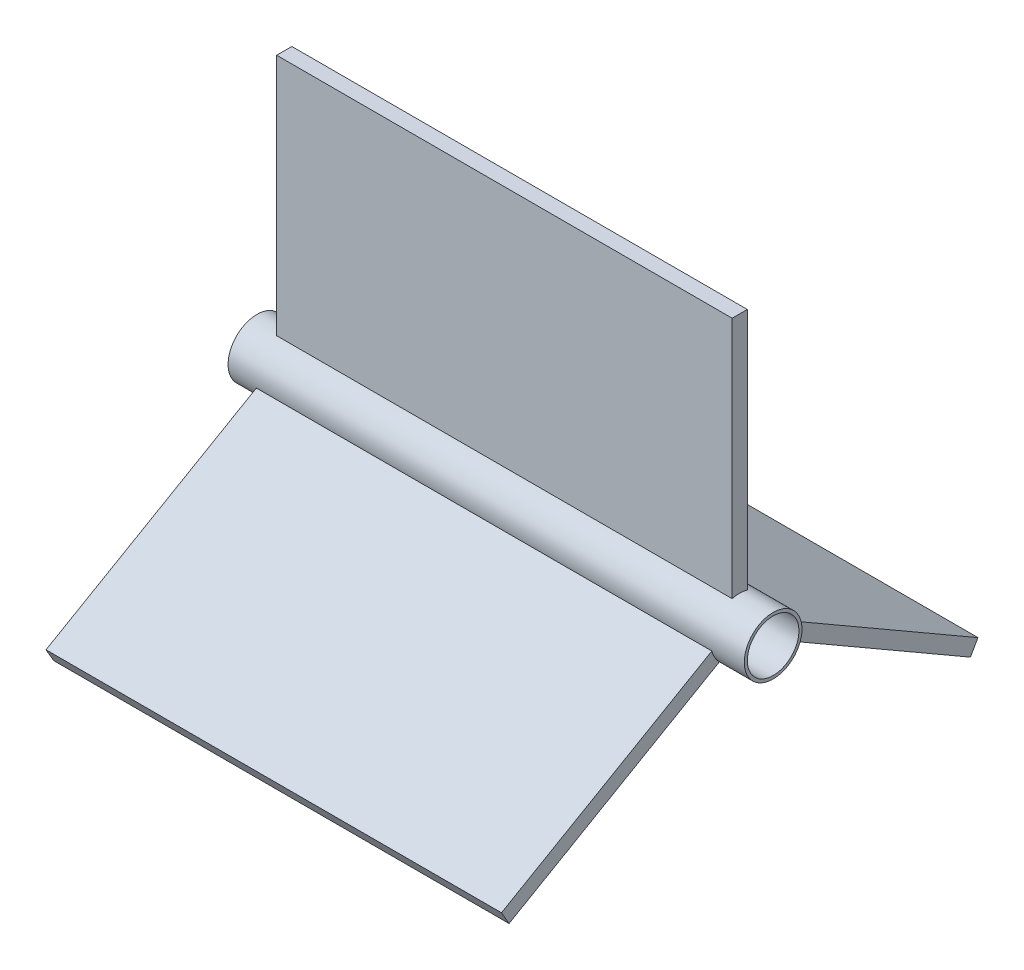
SolidWorks part; units mm, degrees
ref_plane "Alzado" through (0, 0, 0) normal (0, 0, 1) x (1, 0, 0)
ref_plane "Planta" through (0, 0, 0) normal (0, 1, 0) x (1, 0, 0)
ref_plane "Vista lateral" through (0, 0, 0) normal (1, 0, 0) x (0, 0, -1)
sketch "Croquis1" plane through (0, 0, 0) normal (1, 0, 0) x (0, 0, -1)
  circle A0 centre (0, 0) radius 9.5
  dimension "D1" = 19
extrude "Saliente-Extruir1" add sketch "Croquis1" along normal blind 170
ref_plane "Plano1" through (159, 0, 0) normal (1, 0, 0) x (0, 0, -1)
sketch "Croquis2" plane through (0, 0, 0) normal (-1, 0, 0) x (0, 0, 1)
  line L0 (78.4693, -42.4175) -> (75.9693, -46.7476)
  line L1 (-2.5, 9.1652) -> (2.5, 9.1652)
  line L2 (-2.5, 9.1652) -> (-2.5, 89.1652)
  line L3 (-2.5, 89.1652) -> (2.5, 89.1652)
  line L4 (2.5, 9.1652) -> (2.5, 89.1652)
  line L5 (-2.5, 9.1652) -> (2.5, 89.1652) construction
  line L6 (-2.5, 89.1652) -> (2.5, 9.1652) construction
  line L7 (6.6873, -6.7476) -> (75.9693, -46.7476)
  line L8 (9.1873, -2.4175) -> (78.4693, -42.4175)
  line L9 (9.1873, -2.4175) -> (6.6873, -6.7476)
  line L10 (-75.9693, -46.7476) -> (-78.4693, -42.4175)
  line L11 (-9.1873, -2.4175) -> (-78.4693, -42.4175)
  line L12 (-6.6873, -6.7476) -> (-75.9693, -46.7476)
  line L13 (-6.6873, -6.7476) -> (-9.1873, -2.4175)
  circle A0 centre (0, 0) radius 9.5 construction
  point P4 (0, 49.1652)
  point P18 (0, 0)
  dimension "D1" = 5
  dimension "D2" = 80
  dimension "D3" = 3
extrude "Saliente-Extruir2" add sketch "Croquis2" along normal blind 150 from surface starting at plane "Plano1"
sketch "Croquis3" plane through (0, 0, 0) normal (-1, 0, 0) x (0, 0, 1)
  circle A0 centre (0, 0) radius 8.5
  circle A1 centre (0, 0) radius 9.5 construction
  dimension "D1" = 1
extrude "Cortar-Extruir1" cut sketch "Croquis3" against normal through all
equation "\"D2@Croquis2\"=80"
